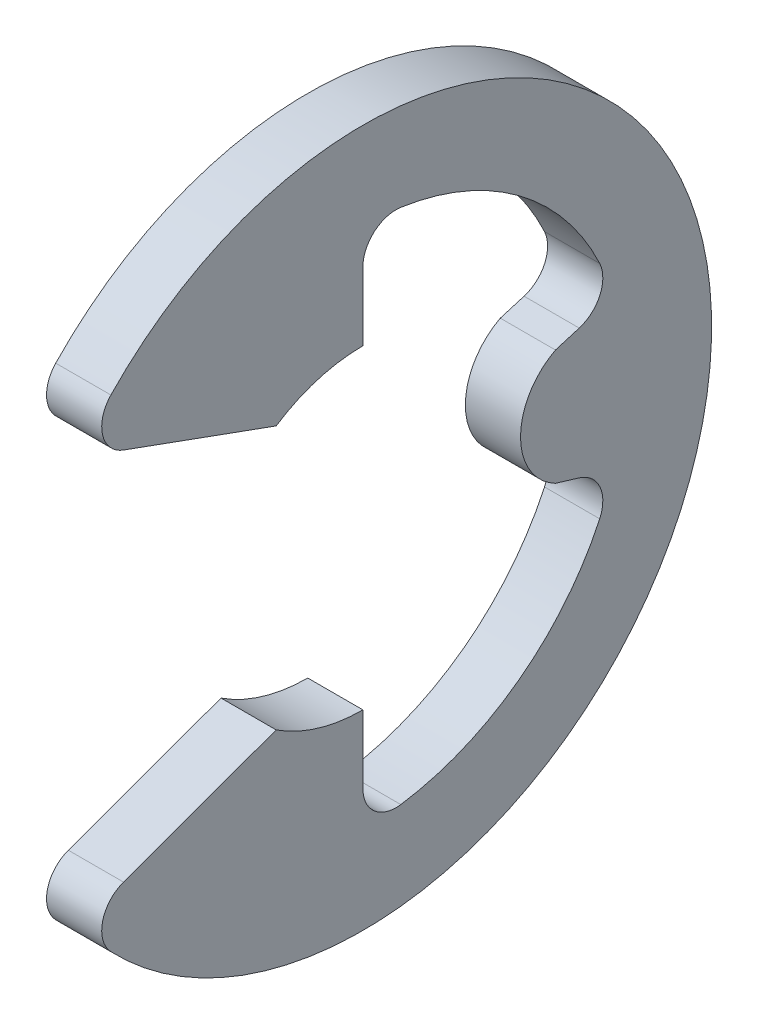
SolidWorks part; units mm, degrees
ref_plane "Front" through (0, 0, 0) normal (0, 0, 1) x (1, 0, 0)
ref_plane "Top" through (0, 0, 0) normal (0, 1, 0) x (1, 0, 0)
ref_plane "Right" through (0, 0, 0) normal (1, 0, 0) x (0, 0, -1)
sketch "Sketch2" plane through (0, 0, 0) normal (1, 0, 0) x (0, 0, -1)
  line L0 (-1.1005, 1.67) -> (-1.1005, -1.67) construction
  circle A0 centre (0, 0) radius 4.425 construction
  circle A1 centre (0, 0) radius 2 construction
  dimension "Ring OD" = 8.85
  dimension "Ring Gap Width" = 3.34
sketch "Sketch3" plane through (0, 0, 0) normal (0, 1, 0) x (1, 0, 0)
  line L0 (0.35, 4.425) -> (-0.35, 4.425) construction
  line L1 (-0.37, -3.0975) -> (0.37, -3.0975) construction
  line L2 (-0.37, -3.0975) -> (-0.37, -3.3442) construction
  line L3 (0, -4.425) -> (0, 4.425) construction
  line L4 (0, -4.425) -> (0, 4.425) construction
  line L5 (0.37, -3.3442) -> (-0.37, -3.3442)
  point P4 (0, -3.0975)
  point P6 (0, 4.425)
  point P13 (0, -3.3442)
  dimension "D1" = 2.655
  dimension "Ring Thickness" = 0.7
  dimension "D2" = 0.2467
sketch "Sketch1" plane through (0, 0, 0) normal (1, 0, 0) x (0, 0, -1)
  line L0 (-3.5973, -2.5769) -> (-1.1005, -1.67)
  line L1 (-3.5973, 2.5769) -> (-1.1005, 1.67)
  line L2 (0, -2) -> (0, -3.3161)
  line L3 (0, 2) -> (0, 3.3161)
  line L4 (1.9157, -0.5745) -> (3.1764, -0.9525)
  line L5 (1.9157, 0.5745) -> (3.1764, 0.9525)
  line L6 (0, 0) -> (-1.625, 0) construction
  line L7 (1.9157, 0.5745) -> (1.9157, -0.5745) construction
  line L8 (-1.1005, 1.67) -> (0, 2) construction
  line L9 (-1.1005, -1.67) -> (0, -2) construction
  line L10 (-1.1005, 1.67) -> (-1.1005, -1.67) construction
  circle A1 centre (0, 0) radius 4.425 construction
  circle A2 centre (0, 0) radius 2 construction
  arc A3 (-3.5973, -2.5769) -> (-3.5973, 2.5769) centre (0, 0) ccw
  arc A4 (-1.1005, 1.67) -> (0, 2) centre (0, 0) cw
  arc A5 (-1.1005, -1.67) -> (0, -2) centre (0, 0) ccw
  arc A6 (1.9157, 0.5745) -> (1.9157, -0.5745) centre (0, 0) cw
  arc A7 (0, -3.3161) -> (3.1764, -0.9525) centre (0, 0) ccw
  arc A8 (3.1764, 0.9525) -> (0, 3.3161) centre (0, 0) ccw
  circle A9 centre (0, 0) radius 2 construction
  point P12 (1.9157, 0)
  dimension "D1" = 3.3161
  dimension "D2" = 2.3879
extrude "Extrude1" add sketch "Sketch1" along normal mid plane 0.7
fillet "Fillet1" radius 0.42 6 edges at (0, -3.3161, 0) (0, 3.3161, 0) (0, -2.5769, 3.5973) (0, 2.5769, 3.5973) (0, -0.9525, -3.1764) (0, 0.9525, -3.1764)
sketch "Sketch4" plane through (0, 0, 0) normal (1, 0, 0) x (0, 0, -1)
  line L1 (0, 2.8655) -> (0, -2.8655)
  arc A1 (2.7448, -0.8231) -> (2.7448, 0.8231) centre (2.8272, 0) cw
  arc A2 (1.9157, -0.5745) -> (1.9157, 0.5745) centre (0, 0) ccw construction
  arc A7 (0.4809, 3.2811) -> (0, 2.8655) centre (0.42, 2.8655) ccw construction
  arc A8 (3.0047, 1.4031) -> (0.4809, 3.2811) centre (0, 0) ccw construction
  arc A9 (2.7448, 0.8231) -> (3.0047, 1.4031) centre (2.6241, 1.2254) ccw construction
  arc A10 (3.0047, -1.4031) -> (2.7448, -0.8231) centre (2.6241, -1.2254) ccw construction
  arc A11 (0.4809, -3.2811) -> (3.0047, -1.4031) centre (0, 0) ccw construction
  arc A12 (0, -2.8655) -> (0.4809, -3.2811) centre (0.42, -2.8655) ccw construction
  arc A13 (0.4809, 3.2811) -> (0, 2.8655) centre (0.42, 2.8655) ccw
  arc A14 (3.0047, 1.4031) -> (0.4809, 3.2811) centre (0, 0) ccw
  arc A15 (2.7448, 0.8231) -> (3.0047, 1.4031) centre (2.6241, 1.2254) ccw
  arc A16 (3.0047, -1.4031) -> (2.7448, -0.8231) centre (2.6241, -1.2254) ccw
  arc A17 (0.4809, -3.2811) -> (3.0047, -1.4031) centre (0, 0) ccw
  arc A18 (0, -2.8655) -> (0.4809, -3.2811) centre (0.42, -2.8655) ccw
extrude "Cut-Extrude1" cut sketch "Sketch4" against normal through all both and the other way through all contours A14 region at (0, 0, -1.2421)
ref_plane "Contact Plane 1" through (0.35, 0, 0) normal (1, 0, 0) x (0, 0, -1)
ref_plane "Contact Plane 2" through (-0.35, 0, 0) normal (-1, 0, 0) x (0, 0, 1)
ref_axis "Center Axis 1" through (5.5843, 0, 0) along (-1, 0, 0)
equation "\"D1@Fillet1\" = \"Ring Thickness@Sketch3\" * .6"
equation "\"D1@Sketch1\" = ( \"Ring OD@Sketch2\" + \"Groove Diameter@Sketch2\" ) / 3.875"
equation "\"D1@Sketch3\"=\"Ring OD@Sketch2\"*.3"
equation "\"D2@Extrude1\"=\"Ring Thickness@Sketch3\""
equation "\"D2@Sketch3\"=\"Groove Width@Sketch3\"/3"
